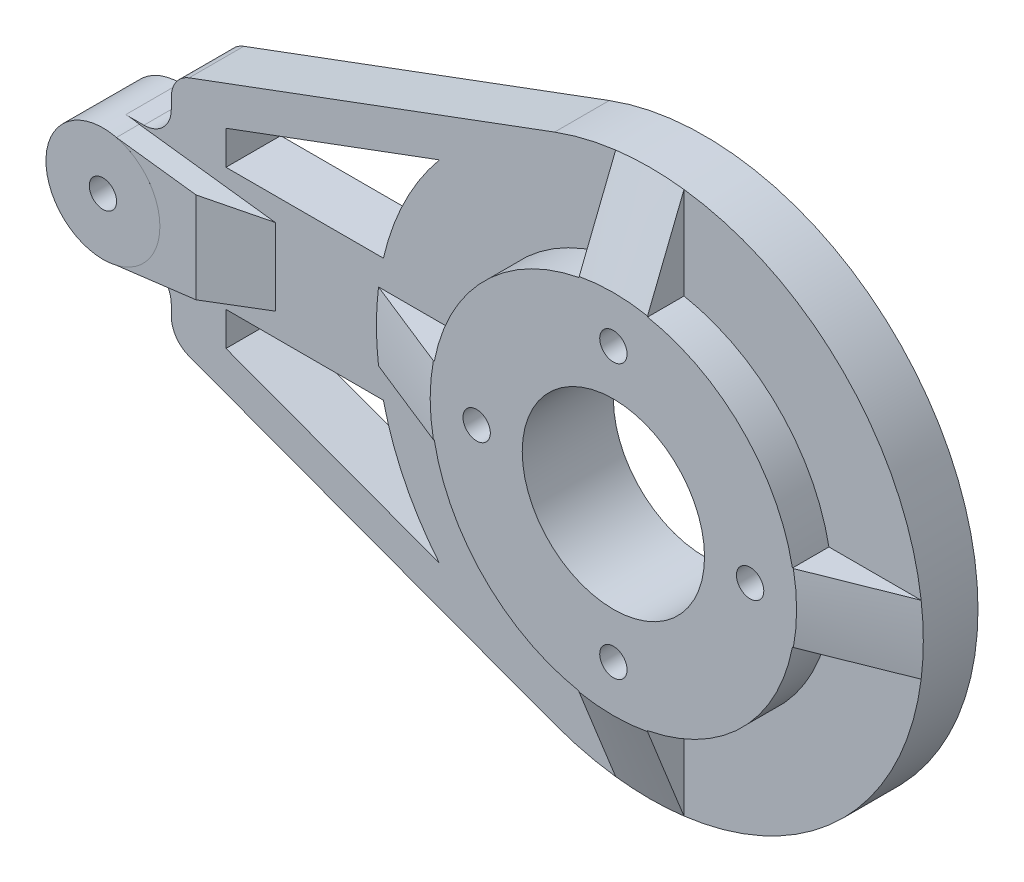
SolidWorks part; units mm, degrees
ref_plane "Front Plane" through (0, 0, 0) normal (0, 0, 1) x (1, 0, 0)
ref_plane "Top Plane" through (0, 0, 0) normal (0, 1, 0) x (1, 0, 0)
ref_plane "Right Plane" through (0, 0, 0) normal (1, 0, 0) x (0, 0, -1)
sketch "Sketch2" plane through (0, 0, 0) normal (0, 0, 1) x (1, 0, 0)
  circle A0 centre (0, 0) radius 20
  circle A1 centre (0, 0) radius 40
  dimension "D1" = 40
  dimension "D2" = 80
extrude "Boss-Extrude1" add sketch "Sketch2" along normal blind 8
sketch "Sketch3" plane through (0, 0, 0) normal (0, 0, -1) x (-1, 0, 0)
  line L0 (0, 0) -> (105, 0) construction
  line L1 (105, -25) -> (105, 25)
  line L2 (105, 25) -> (20.8942, 56.2444)
  line L3 (105, -25) -> (20.8942, -56.2444)
  arc A0 (20.8942, 56.2444) -> (20.8942, -56.2444) centre (0, 0) ccw
  circle A1 centre (0, 0) radius 20
  point P7 (105, 0)
  dimension "D1" = 120
  dimension "D2" = 105
  dimension "D3" = 50
extrude "Boss-Extrude2" add sketch "Sketch3" along normal blind 12
sketch "Sketch4" plane through (0, 0, -12) normal (0, 0, -1) x (-1, 0, 0)
  line L0 (0, 0) -> (0, 30) construction
  circle A0 centre (0, 30) radius 7.5
  circle A1 centre (30, 0) radius 7.5
  circle A2 centre (0, -30) radius 7.5
  circle A3 centre (-30, 0) radius 7.5
  point P13 (0, 0)
  dimension "D2" = 15
  dimension "D1" = 30
  dimension "D3" = 4
extrude "Cut-Extrude1" cut sketch "Sketch4" against normal blind 10
sketch "Sketch5" plane through (0, 0, -2) normal (0, 0, -1) x (-1, 0, 0)
  circle A0 centre (30, 0) radius 3
  circle A1 centre (0, -30) radius 3
  circle A2 centre (-30, 0) radius 3
  circle A3 centre (0, 30) radius 3
  point P12 (0, 0)
  dimension "D1" = 6
  dimension "D2" = 4
extrude "Cut-Extrude2" cut sketch "Sketch5" against normal blind 29
sketch "Sketch6" plane through (0, 0, 0) normal (0, 0, 1) x (1, 0, 0)
  line L0 (39.2906, -7.5) -> (59.5294, -7.5)
  line L1 (39.2906, 7.5) -> (59.5294, 7.5)
  line L2 (-7.5, 39.2906) -> (-7.5, 59.5294)
  line L3 (7.5, 39.2906) -> (7.5, 59.5294)
  line L4 (-7.5, -39.2906) -> (-7.5, -59.5294)
  line L5 (7.5, -39.2906) -> (7.5, -59.5294)
  line L6 (-39.2906, 7.5) -> (-59.5294, 7.5)
  line L7 (-39.2906, -7.5) -> (-59.5294, -7.5)
  arc A1 (7.5, 39.2906) -> (-7.5, 39.2906) centre (0, 0) ccw
  arc A5 (7.5, 59.5294) -> (-7.5, 59.5294) centre (0, 0) ccw
  arc A6 (59.5294, -7.5) -> (59.5294, 7.5) centre (0, 0) ccw
  arc A7 (39.2906, -7.5) -> (39.2906, 7.5) centre (0, 0) ccw
  arc A8 (-7.5, -59.5294) -> (7.5, -59.5294) centre (0, 0) ccw
  arc A9 (-7.5, -39.2906) -> (7.5, -39.2906) centre (0, 0) ccw
  arc A10 (-59.5294, 7.5) -> (-59.5294, -7.5) centre (0, 0) ccw
  arc A11 (-39.2906, 7.5) -> (-39.2906, -7.5) centre (0, 0) ccw
  point P10 (0, 48.2861)
  point P13 (-7.5, 49.41)
  point P16 (7.5, 49.41)
  point P25 (0, 0)
  dimension "D1" = 15
  dimension "D2" = 4
extrude "Boss-Extrude3" add sketch "Sketch6" along direction (0, 0, 1) on the side of the normal blind 8
chamfer "Chamfer3" distance 8 angle 68 4 edges at (0, 60, 8) (60, 0, 8) (-60, 0, 8) (0, -60, 8) first distance on face at (15.8462, 0, 1.5) first distance on face at (-59.7647, 0, 4)
sketch "Sketch7" plane through (0, 0, -12) normal (0, 0, -1) x (-1, 0, 0)
  line L0 (105, 0) -> (115, 0) construction
  line L1 (105, -25) -> (105, 25) construction
  line L2 (115, 12.5) -> (105, 12.5)
  line L3 (105, 12.5) -> (105, -12.5)
  line L4 (105, -12.5) -> (115, -12.5)
  arc A0 (115, -12.5) -> (115, 12.5) centre (115, 0) ccw
  dimension "D2" = 25
  dimension "D1" = 10
extrude "Boss-Extrude4" add sketch "Sketch7" against normal up to surface (12 mm away) up to face at (-40.8222, 0, 0)
fillet "Fillet1" radius 6 4 edges at (-105, 25, -6) (-105, 12.5, -6) (-105, -25, -6) (-105, -12.5, -6)
sketch "Sketch8" plane through (0, 0, -12) normal (0, 0, -1) x (-1, 0, 0)
  line L1 (118.7786, 6.485) -> (111.2731, 6.5149)
  line L2 (111.2731, 6.5149) -> (107.4945, 0.0298)
  line L3 (107.4945, 0.0298) -> (111.2214, -6.485)
  line L4 (111.2214, -6.485) -> (118.7269, -6.5149)
  line L5 (118.7269, -6.5149) -> (122.5055, -0.0298)
  line L6 (122.5055, -0.0298) -> (118.7786, 6.485)
  circle A0 centre (115, 0) radius 6.5 construction
  dimension "D1" = 13
extrude "Cut-Extrude3" cut sketch "Sketch8" against normal blind 10
sketch "Sketch9" plane through (0, 0, -2) normal (0, 0, -1) x (-1, 0, 0)
  circle A0 centre (115, 0) radius 3
  dimension "D1" = 6
extrude "Cut-Extrude4" cut sketch "Sketch9" against normal blind 6
sketch "Sketch10" plane through (0, 0, 0) normal (0, 0, 1) x (1, 0, 0)
  line L2 (-20.8942, -56.2444) -> (-101.0894, -26.4527) construction
  line L3 (-58.4615, -13.5) -> (-93, -13.5)
  line L4 (-59.5294, -7.5) -> (-39.2906, -7.5) construction
  line L6 (-93, -13.5) -> (-93, -20.9237)
  line L7 (-60, 0) -> (-127.5, 0) construction
  line L9 (-93, 20.9237) -> (-46.1679, 38.3213)
  line L10 (-93, 13.5) -> (-93, 20.9237)
  line L11 (-93, -20.9237) -> (-46.1679, -38.3213)
  line L12 (-58.4615, 13.5) -> (-93, 13.5)
  arc A0 (-58.4615, -13.5) -> (-46.1679, -38.3213) centre (0, 0) ccw
  arc A2 (-59.5294, 7.5) -> (-59.5294, -7.5) centre (0, 0) ccw construction
  arc A3 (-115, 12.5) -> (-115, -12.5) centre (-115, 0) ccw construction
  arc A4 (-58.4615, 13.5) -> (-46.1679, 38.3213) centre (0, 0) cw
  dimension "D1" = 60
  dimension "D3" = 8
  dimension "D4" = 6
extrude "Cut-Extrude5" cut sketch "Sketch10" against normal blind 22
sketch "Sketch11" plane through (0, 0, -12) normal (0, 0, -1) x (-1, 0, 0)
  point P0 (0, 0)
ref_axis "Base_Axis_Coordinate" through (0, 0, 8) along (0, 0, -1)
sketch "Sketch12" plane through (0, 0, 0) normal (0, 0, 1) x (1, 0, 0)
  circle A0 centre (-115, 0) radius 3
  circle A1 centre (-115, 0) radius 12.5
extrude "Boss-Extrude5" add sketch "Sketch12" along normal blind 5
sketch "Sketch13" plane through (0, 0, 0) normal (0, 0, 1) x (1, 0, 0)
  line L0 (-74.7433, 7.5) -> (-112.0372, 12.1444)
  line L6 (-74.7433, 7.5) -> (-74.7433, -7.5)
  line L7 (-74.7433, -7.5) -> (-112.0372, -12.1444)
  arc A2 (-112.0372, -12.1444) -> (-112.0372, 12.1444) centre (-115, 0) ccw
extrude "Boss-Extrude6" add sketch "Sketch13" along normal blind 5
chamfer "Chamfer7" distance 8 angle 68 1 edges at (-74.7433, 0, 5) first distance on face at (-74.7433, 0, 2.5)
